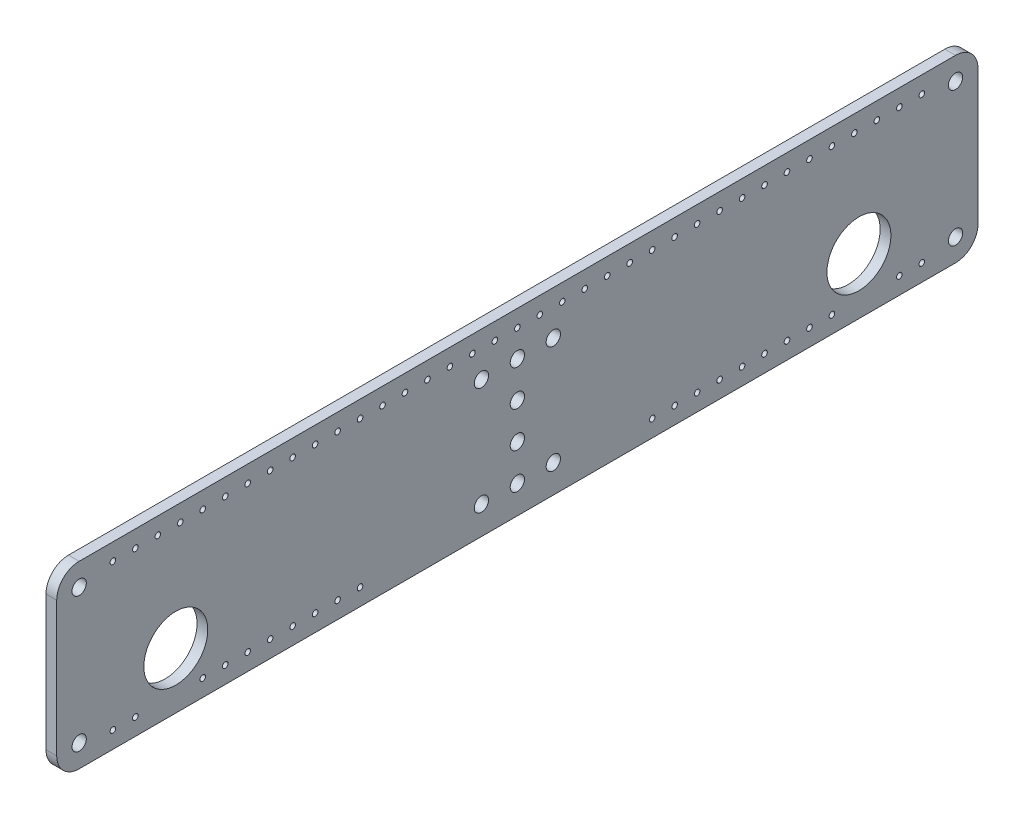
SolidWorks part; units mm, degrees
ref_plane "Front Plane" through (0, 0, 0) normal (0, 0, 1) x (1, 0, 0)
ref_plane "Top Plane" through (0, 0, 0) normal (0, 1, 0) x (1, 0, 0)
ref_plane "Right Plane" through (0, 0, 0) normal (1, 0, 0) x (0, 0, -1)
sketch "Sketch2" plane through (0, 0, 0) normal (1, 0, 0) x (0, 0, -1)
  line L0 (-23.4723, 28.6683) -> (-23.4723, -31.3317)
  line L1 (-13.4723, 38.6683) -> (376.5277, 38.6683)
  line L2 (-13.4723, -41.3317) -> (376.5277, -41.3317)
  line L3 (386.5277, 28.6683) -> (386.5277, -31.3317)
  circle A1 centre (29.5277, -16.3317) radius 14.225
  circle A2 centre (333.5277, -16.3317) radius 14.225
  arc A15 (-23.4723, 28.6683) -> (-13.4723, 38.6683) centre (-13.4723, 28.6683) cw
  arc A16 (-13.4723, -41.3317) -> (-23.4723, -31.3317) centre (-13.4723, -31.3317) cw
  arc A17 (386.5277, 28.6683) -> (376.5277, 38.6683) centre (376.5277, 28.6683) ccw
  arc A18 (376.5277, -41.3317) -> (386.5277, -31.3317) centre (376.5277, -31.3317) ccw
  circle A59 centre (181.5277, -28.7717) radius 3.18
  circle A60 centre (197.5277, -28.7717) radius 3.18
  circle A63 centre (197.5277, 19.2283) radius 3.18
  circle A64 centre (181.5277, -12.7717) radius 3.18
  circle A65 centre (181.5277, 3.2283) radius 3.18
  circle A66 centre (181.5277, 19.2283) radius 3.18
  circle A67 centre (165.5277, -28.7717) radius 3.18
  circle A68 centre (165.5277, 19.2283) radius 3.18
  circle A69 centre (197.5277, -12.7717) radius 3.18 [skipped]
  circle A70 centre (197.5277, 3.2283) radius 3.18 [skipped]
  circle A71 centre (-8.4723, 31.1683) radius 1.25 construction
  circle A152 centre (1.5277, 31.1683) radius 1.25
  circle A153 centre (11.5277, 31.1683) radius 1.25
  circle A154 centre (21.5277, 31.1683) radius 1.25
  circle A155 centre (31.5277, 31.1683) radius 1.25
  circle A156 centre (41.5277, 31.1683) radius 1.25
  circle A157 centre (51.5277, 31.1683) radius 1.25
  circle A158 centre (61.5277, 31.1683) radius 1.25
  circle A159 centre (71.5277, 31.1683) radius 1.25
  circle A160 centre (81.5277, 31.1683) radius 1.25
  circle A161 centre (91.5277, 31.1683) radius 1.25
  circle A162 centre (101.5277, 31.1683) radius 1.25
  circle A163 centre (111.5277, 31.1683) radius 1.25
  circle A164 centre (121.5277, 31.1683) radius 1.25
  circle A165 centre (131.5277, 31.1683) radius 1.25
  circle A166 centre (141.5277, 31.1683) radius 1.25
  circle A167 centre (151.5277, 31.1683) radius 1.25
  circle A168 centre (161.5277, 31.1683) radius 1.25
  circle A169 centre (171.5277, 31.1683) radius 1.25
  circle A170 centre (181.5277, 31.1683) radius 1.25
  circle A171 centre (191.5277, 31.1683) radius 1.25
  circle A172 centre (201.5277, 31.1683) radius 1.25
  circle A173 centre (211.5277, 31.1683) radius 1.25
  circle A174 centre (221.5277, 31.1683) radius 1.25
  circle A175 centre (231.5277, 31.1683) radius 1.25
  circle A176 centre (241.5277, 31.1683) radius 1.25
  circle A177 centre (251.5277, 31.1683) radius 1.25
  circle A178 centre (261.5277, 31.1683) radius 1.25
  circle A179 centre (271.5277, 31.1683) radius 1.25
  circle A180 centre (281.5277, 31.1683) radius 1.25
  circle A181 centre (291.5277, 31.1683) radius 1.25
  circle A182 centre (301.5277, 31.1683) radius 1.25
  circle A183 centre (311.5277, 31.1683) radius 1.25
  circle A184 centre (321.5277, 31.1683) radius 1.25
  circle A185 centre (331.5277, 31.1683) radius 1.25
  circle A186 centre (341.5277, 31.1683) radius 1.25
  circle A187 centre (351.5277, 31.1683) radius 1.25
  circle A188 centre (361.5277, 31.1683) radius 1.25
  circle A190 centre (1.5277, -33.8317) radius 1.25
  circle A191 centre (11.5277, -33.8317) radius 1.25
  circle A194 centre (41.5277, -33.8317) radius 1.25
  circle A195 centre (51.5277, -33.8317) radius 1.25
  circle A196 centre (61.5277, -33.8317) radius 1.25
  circle A197 centre (71.5277, -33.8317) radius 1.25
  circle A198 centre (81.5277, -33.8317) radius 1.25
  circle A199 centre (91.5277, -33.8317) radius 1.25
  circle A200 centre (101.5277, -33.8317) radius 1.25
  circle A201 centre (111.5277, -33.8317) radius 1.25
  circle A214 centre (241.5277, -33.8317) radius 1.25
  circle A215 centre (251.5277, -33.8317) radius 1.25
  circle A216 centre (261.5277, -33.8317) radius 1.25
  circle A217 centre (271.5277, -33.8317) radius 1.25
  circle A218 centre (281.5277, -33.8317) radius 1.25
  circle A219 centre (291.5277, -33.8317) radius 1.25
  circle A220 centre (301.5277, -33.8317) radius 1.25
  circle A221 centre (311.5277, -33.8317) radius 1.25
  circle A222 centre (321.5277, -33.8317) radius 1.25
  circle A225 centre (351.5277, -33.8317) radius 1.25
  circle A226 centre (361.5277, -33.8317) radius 1.25
  circle A229 centre (181.5277, -33.8317) radius 1.25 [skipped]
  circle A230 centre (201.5277, -33.8317) radius 1.25 [skipped]
  circle A231 centre (161.5277, -33.8317) radius 1.25 [skipped]
  circle A232 centre (151.5277, -33.8317) radius 1.25 [skipped]
  circle A233 centre (141.5277, -33.8317) radius 1.25 [skipped]
  circle A234 centre (131.5277, -33.8317) radius 1.25 [skipped]
  circle A235 centre (171.5277, -33.8317) radius 1.25 [skipped]
  circle A236 centre (191.5277, -33.8317) radius 1.25 [skipped]
  circle A237 centre (211.5277, -33.8317) radius 1.25 [skipped]
  circle A238 centre (221.5277, -33.8317) radius 1.25 [skipped]
  circle A239 centre (231.5277, -33.8317) radius 1.25 [skipped]
  circle A240 centre (31.5277, -33.8317) radius 1.25 [skipped]
  circle A241 centre (21.5277, -33.8317) radius 1.25 [skipped]
  circle A242 centre (331.5277, -33.8317) radius 1.25 [skipped]
  circle A243 centre (341.5277, -33.8317) radius 1.25 [skipped]
  circle A244 centre (-13.4723, -31.3317) radius 3.18
  circle A245 centre (-13.4723, 28.6683) radius 3.18
  circle A246 centre (376.5277, -31.3317) radius 3.18
  circle A247 centre (376.5277, 28.6683) radius 3.18
  circle A248 centre (371.5277, 31.1683) radius 1.25 [skipped]
  circle A249 centre (371.5277, -33.8317) radius 1.25 [skipped]
  circle A250 centre (-8.4723, -33.8317) radius 1.25 [skipped]
  circle A257 centre (121.5277, -33.8317) radius 1.25 [skipped]
  point P32 (-23.4723, 38.6683)
  point P35 (-23.4723, -41.3317)
  point P40 (386.5277, -41.3317)
  point P123 (181.5277, -41.3317)
  dimension "D3" = 25
  dimension "D7" = 10
  dimension "D8" = 10
  dimension "D9" = 10
  dimension "D10" = 10
  dimension "D11" = 7.5
  dimension "D13" = 12.56
  dimension "D1" = 80
  dimension "D2" = 410
  dimension "D4" = 53
  dimension "D5" = 25
  dimension "D6" = 53
  dimension "D12" = 15
  dimension "D14" = 205
  dimension "D15" = 2
  dimension "D16" = 4
  dimension "D17" = 2
  dimension "D18" = 39
  dimension "D19" = 2
extrude "Boss-Extrude1" add sketch "Sketch2" along normal blind 4.7625
